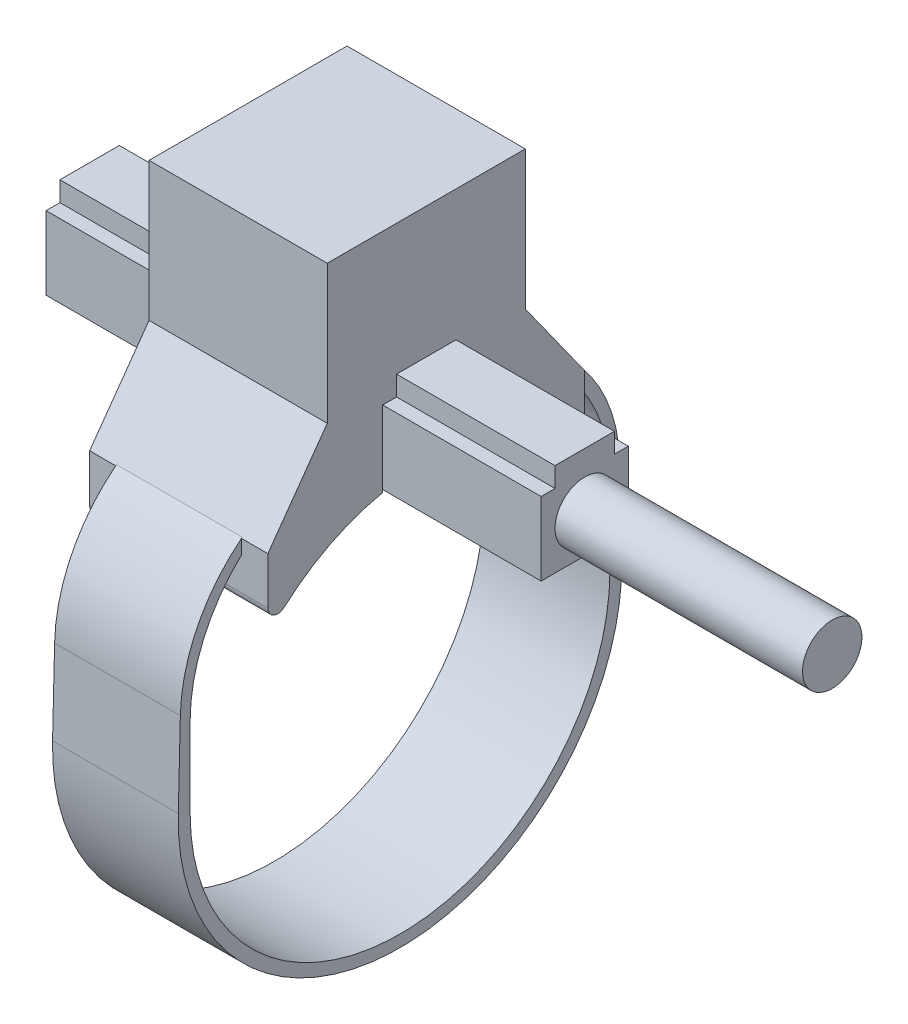
SolidWorks part; units mm, degrees
ref_plane "前视基准面" through (0, 0, 0) normal (0, 0, 1) x (1, 0, 0)
ref_plane "上视基准面" through (0, 0, 0) normal (0, 1, 0) x (1, 0, 0)
ref_plane "右视基准面" through (0, 0, 0) normal (1, 0, 0) x (0, 0, -1)
ref_plane "基准面4" through (11.5, 0, 0) normal (1, 0, 0) x (0, 0, -1)
sketch "草图1" plane through (11.5, 0, 0) normal (1, 0, 0) x (0, 0, -1)
  line L0 (-8, 10.7) -> (-8, 8.3181)
  line L1 (-2.2, 10.4714) -> (-2.2, 13.9)
  line L2 (-2.2, 13.9) -> (-1.5, 13.9)
  line L3 (-1.5, 13.9) -> (-1.5, 14.9)
  line L4 (-1.5, 14.9) -> (1.5, 14.9)
  line L5 (1.5, 14.9) -> (1.5, 13.9)
  line L6 (1.5, 13.9) -> (2.2, 13.9)
  line L7 (2.2, 13.9) -> (2.2, 10.4714)
  line L8 (8, 8.3181) -> (8, 10.7)
  line L9 (8, 10.7) -> (5, 14.9)
  line L10 (5, 14.9) -> (5, 21.9)
  line L11 (5, 21.9) -> (-5, 21.9)
  line L12 (-5, 21.9) -> (-5, 14.9)
  line L13 (-5, 14.9) -> (-8, 10.7)
  arc A0 (-8, 8.3181) -> (-7.1652, 7.9467) centre (-7.5, 8.3181) ccw
  arc A1 (-7.1652, 7.9467) -> (-2.2, 10.4714) centre (0, 0) cw
  arc A2 (2.2, 10.4714) -> (7.1652, 7.9467) centre (0, 0) cw
  arc A3 (7.1652, 7.9467) -> (8, 8.3181) centre (7.5, 8.3181) ccw
extrude "凸台-拉伸1" add sketch "草图1" against normal blind 4.5 and the other way blind 4.5
sketch "草图2" plane through (11.5, 0, 0) normal (1, 0, 0) x (0, 0, -1)
  line L0 (11.1967, 0.2717) -> (11.0941, 4.4989)
  line L1 (2.8965, 12.5) -> (-2.8965, 12.5)
  line L2 (-11.0941, 4.4989) -> (-11.1967, 0.2717)
  line L3 (10.6, 0) -> (10.6, 4)
  line L4 (2.4, 12.2) -> (-2.4, 12.2)
  line L5 (-10.6, 4) -> (-10.6, 0)
  arc A0 (-11.1967, 0.2717) -> (11.1967, 0.2717) centre (0, 0) ccw
  arc A1 (11.0941, 4.4989) -> (2.8965, 12.5) centre (2.8965, 4.3) ccw
  arc A2 (-2.8965, 12.5) -> (-11.0941, 4.4989) centre (-2.8965, 4.3) ccw
  arc A3 (-10.6, 0) -> (10.6, 0) centre (0, 0) ccw
  arc A4 (10.6, 4) -> (2.4, 12.2) centre (2.4, 4) ccw
  arc A5 (-2.4, 12.2) -> (-10.6, 4) centre (-2.4, 4) ccw
extrude "凸台-拉伸2" add sketch "草图2" against normal blind 3.175 and the other way blind 3.175
sketch "草图3" plane through (11.5, 0, 0) normal (1, 0, 0) x (0, 0, -1)
  line L0 (-2.2, 14.3) -> (-2.2, 10.6)
  line L1 (-2.2, 10.6) -> (2.2, 10.6)
  line L2 (2.2, 10.6) -> (2.2, 14.3)
  line L3 (2.2, 14.3) -> (1.5, 14.3)
  line L4 (1.5, 14.3) -> (1.5, 15.3)
  line L5 (1.5, 15.3) -> (-1.5, 15.3)
  line L6 (-1.5, 15.3) -> (-1.5, 14.3)
  line L7 (-1.5, 14.3) -> (-2.2, 14.3)
extrude "凸台-拉伸3" add sketch "草图3" against normal blind 12.5 and the other way blind 12.5
sketch "草图4" plane through (11.5, 0, 0) normal (1, 0, 0) x (0, 0, -1)
  circle A0 centre (0, 12.55) radius 1.5
extrude "凸台-拉伸4" add sketch "草图4" along normal blind 25
ref_plane "基准面5" through (7.1, 0, 0) normal (1, 0, 0) x (0, 0, -1)
ref_plane "CS1_M XY" through (0, 0, 0) normal (1, 0, 0) x (0, 0, -1)
ref_plane "CS1_M XZ" through (0, 0, 0) normal (0, -1, 0) x (-1, 0, 0)
ref_plane "CS1_M YZ" through (0, 0, 0) normal (0, 0, -1) x (-1, 0, 0)
ref_axis "CS1_M X" through (0, 0, 80.9) along (0, 0, -1)
ref_axis "CS1_M Y" through (0, -50, 0) along (0, 1, 0)
ref_axis "CS1_M Z" through (80.9, 0, 0) along (-1, 0, 0)
sketch3d "CS1_M"
  point P0 (0, 0, 0)
